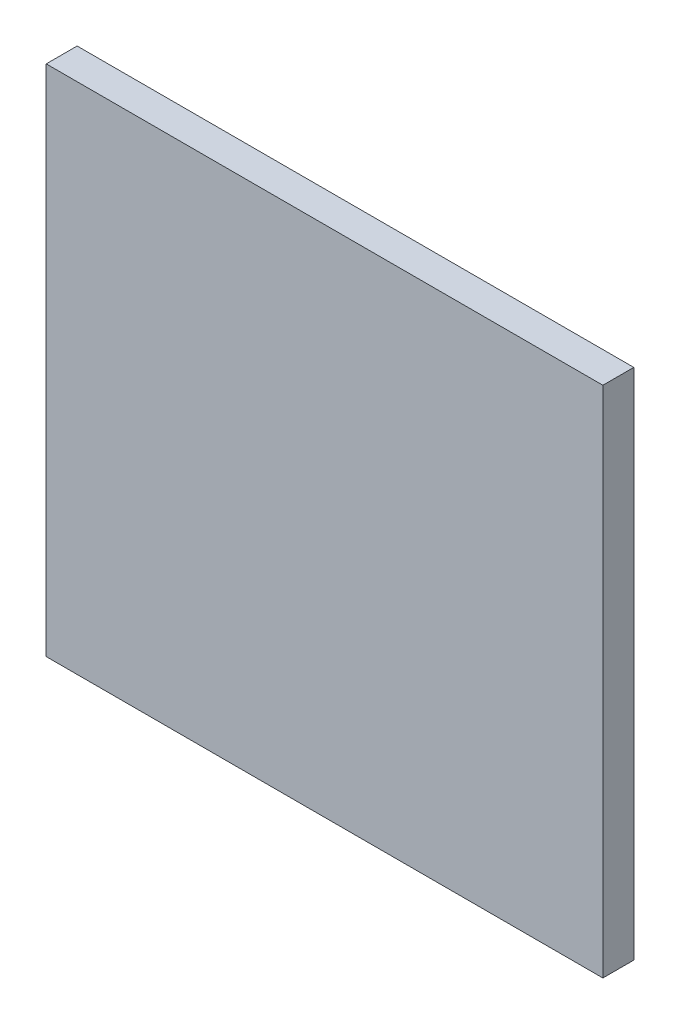
SolidWorks part; units mm, degrees
ref_plane "Front Plane" through (0, 0, 0) normal (0, 0, 1) x (1, 0, 0)
ref_plane "Top Plane" through (0, 0, 0) normal (0, 1, 0) x (1, 0, 0)
ref_plane "Right Plane" through (0, 0, 0) normal (1, 0, 0) x (0, 0, -1)
sketch "Sketch1" plane through (0, 0, 0) normal (0, 0, 1) x (1, 0, 0)
  line L1 (-45, -41.5) -> (45, -41.5)
  line L2 (-45, -41.5) -> (-45, 41.5)
  line L3 (-45, 41.5) -> (45, 41.5)
  line L4 (45, -41.5) -> (45, 41.5)
  line L5 (-45, -41.5) -> (45, 41.5) construction
  line L6 (-45, 41.5) -> (45, -41.5) construction
  point P0 (0, 0)
  dimension "D1" = 83
  dimension "D2" = 90
extrude "Boss-Extrude1" add sketch "Sketch1" along normal blind 5
